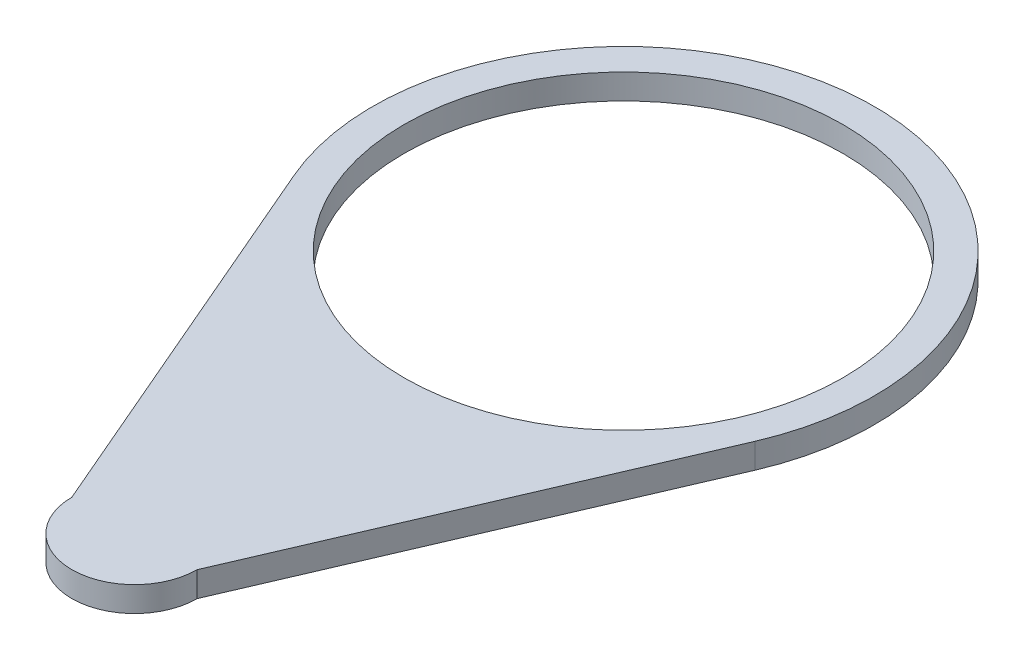
SolidWorks part; units mm, degrees
ref_plane "Front Plane" through (0, 0, 0) normal (0, 0, 1) x (1, 0, 0)
ref_plane "Top Plane" through (0, 0, 0) normal (0, 1, 0) x (1, 0, 0)
ref_plane "Right Plane" through (0, 0, 0) normal (1, 0, 0) x (0, 0, -1)
sketch "Sketch1" plane through (0, 0, 0) normal (0, 1, 0) x (1, 0, 0)
  line L0 (-18.3733, 31.0991) -> (-5, 0)
  line L1 (0, 120.2958) -> (0, -44.3308) construction
  line L2 (18.3733, 31.0991) -> (5, 0)
  arc A0 (-5, 0) -> (5, 0) centre (0, 0) ccw
  circle A1 centre (0, 39) radius 17.5
  arc A2 (18.3733, 31.0991) -> (-18.3733, 31.0991) centre (0, 39) ccw
  dimension "D1" = 35
  dimension "D2" = 40
  dimension "D3" = 5
  dimension "D4" = 39
extrude "Boss-Extrude1" add sketch "Sketch1" along normal blind 2
